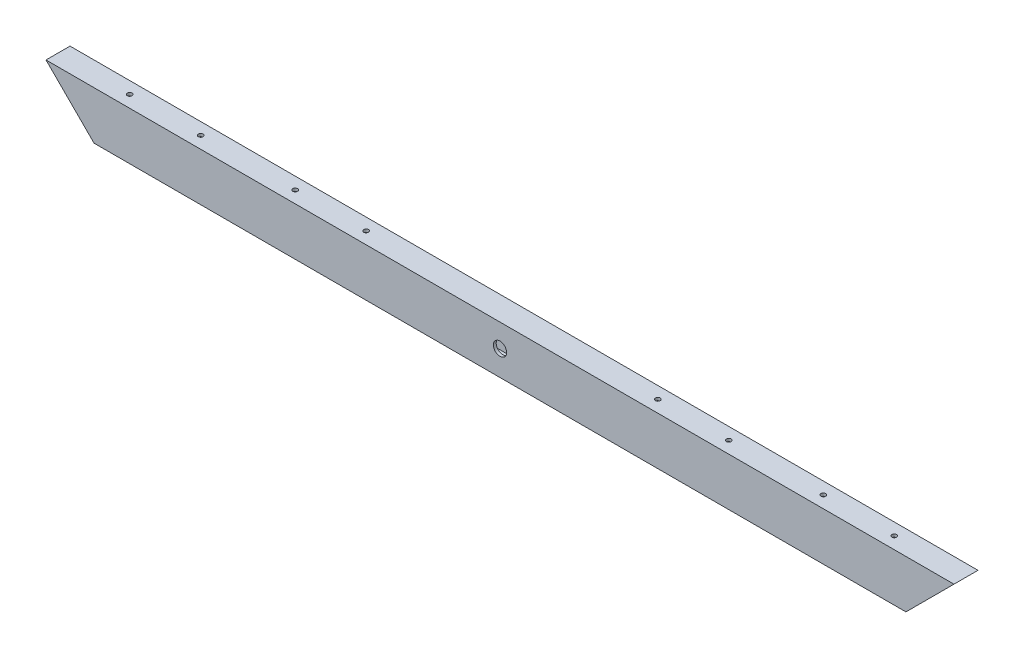
SolidWorks part; units mm, degrees
ref_plane "Front Plane" through (0, 0, 0) normal (0, 0, 1) x (1, 0, 0)
ref_plane "Top Plane" through (0, 0, 0) normal (0, 1, 0) x (1, 0, 0)
ref_plane "Right Plane" through (0, 0, 0) normal (1, 0, 0) x (0, 0, -1)
sketch "Sketch1" plane through (0, 0, 0) normal (0, 0, 1) x (1, 0, 0)
  line L0 (-50.8, 50.8) -> (0, 0)
  line L1 (0, 0) -> (858.4, 0)
  line L3 (-50.8, 50.8) -> (909.2, 50.8)
  line L5 (909.2, 50.8) -> (858.4, 0)
  line L6 (429.2, 50.8) -> (429.2, 0) construction
  circle A0 centre (429.2, 26.4) radius 7
  dimension "D6" = 14
  dimension "D1" = 45
  dimension "D2" = 45
  dimension "D3" = 960
  dimension "D4" = 50.8
  dimension "D5" = 480
  dimension "D7" = 24.4
extrude "Boss-Extrude1" add sketch "Sketch1" along normal blind 25.4
sketch "Sketch3" plane through (0, 0, 0) normal (1, 0, 0) x (0, 0, -1)
  line L0 (-25.4, 0) -> (-25.4, 50.8) construction
  line L1 (-22.4, 47.8) -> (-3, 47.8)
  line L2 (-22.4, 47.8) -> (-22.4, 3)
  line L3 (-22.4, 3) -> (-3, 3)
  line L4 (-3, 47.8) -> (-3, 3)
  line L5 (0, 0) -> (0, 50.8) construction
  line L6 (-25.4, 50.8) -> (0, 50.8) construction
  line L7 (-25.4, 0) -> (0, 0) construction
  dimension "D1" = 3
  dimension "D2" = 3
  dimension "D3" = 3
  dimension "D4" = 3
extrude "Cut-Extrude1" cut sketch "Sketch3" against normal blind 201.4 and the other way blind 1046.4
sketch "Sketch4" plane through (0, 50.8, 0) normal (0, 1, 0) x (1, 0, 0)
  line L0 (-50.8, -25.4) -> (-50.8, 0) construction
  line L1 (909.2, -25.4) -> (909.2, 0) construction
  line L2 (25, -12.7) -> (833.4, -12.7) construction
  line L3 (909.2, 0) -> (-50.8, 0) construction
  circle A0 centre (25, -12.7) radius 2.5
  circle A1 centre (100, -12.7) radius 2.5
  circle A2 centre (200, -12.7) radius 2.5
  circle A3 centre (275, -12.7) radius 2.5
  circle A4 centre (833.4, -12.7) radius 2.5
  circle A5 centre (758.4, -12.7) radius 2.5
  circle A6 centre (658.4, -12.7) radius 2.5
  circle A7 centre (583.4, -12.7) radius 2.5
  point P22 (0, 0)
  dimension "D9" = 5
  dimension "D10" = 5
  dimension "D11" = 5
  dimension "D12" = 5
  dimension "D13" = 5
  dimension "D14" = 5
  dimension "D15" = 5
  dimension "D16" = 5
  dimension "D1" = 75.8
  dimension "D2" = 75.8
  dimension "D3" = 75
  dimension "D4" = 100
  dimension "D5" = 75
  dimension "D6" = 75
  dimension "D7" = 100
  dimension "D8" = 75
  dimension "D17" = 12.7
extrude "Cut-Extrude2" cut sketch "Sketch4" against normal blind 22 and the other way blind 22
